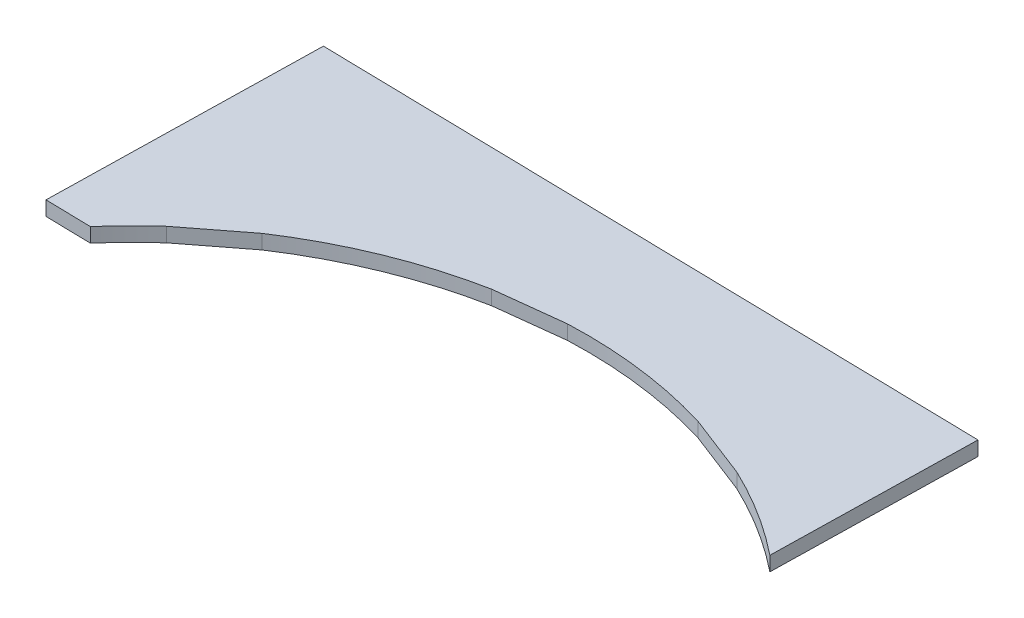
SolidWorks part; units mm, degrees
material "Balsa"
ref_plane "Front Plane" through (0, 0, 0) normal (0, 0, 1) x (1, 0, 0)
ref_plane "Top Plane" through (0, 0, 0) normal (0, 1, 0) x (1, 0, 0)
ref_plane "Right Plane" through (0, 0, 0) normal (1, 0, 0) x (0, 0, -1)
sketch "Sketch1" plane through (0, 0, 0) normal (0, 1, 0) x (1, 0, 0)
  line L0 (-12.8843, 57.5899) -> (-32.8801, 58.0016)
  line L5 (-32.8801, 58.0016) -> (-30.4097, 177.9762)
  line L6 (-30.4097, 177.9762) -> (264.5278, 171.9031)
  line L7 (264.5278, 171.9031) -> (262.6746, 81.9031)
  line L17 (3.8471, 74.5464) -> (27.5977, 92.8811)
  line L18 (99.6149, 122.2056) -> (129.6149, 125.6852)
  line L19 (195.598, 117.2478) -> (223.6208, 106.3964)
  arc A0 (-12.8843, 57.5899) -> (3.8471, 74.5464) centre (137.592, -74.1557) cw
  arc A1 (27.5977, 92.8811) -> (99.6149, 122.2056) centre (137.592, -74.1557) cw
  arc A2 (129.6149, 125.6852) -> (195.598, 117.2478) centre (137.592, -74.1557) cw
  arc A3 (223.6208, 106.3964) -> (262.6746, 81.9031) centre (137.592, -74.1557) cw
  dimension "D5" = 200
  dimension "D1" = 295
  dimension "D2" = 20
  dimension "D3" = 120
  dimension "D4" = 90
extrude "Boss-Extrude1" add sketch "Sketch1" along normal blind 6.35
